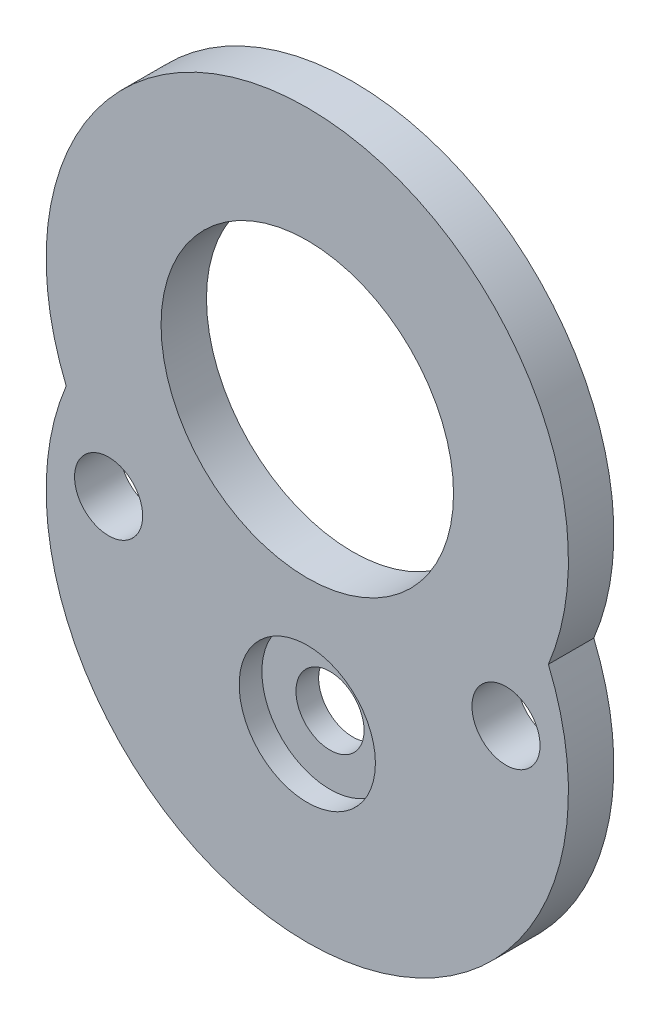
SolidWorks part; units mm, degrees
ref_plane "前视基准面" through (0, 0, 0) normal (0, 0, 1) x (1, 0, 0)
ref_plane "上视基准面" through (0, 0, 0) normal (0, 1, 0) x (1, 0, 0)
ref_plane "右视基准面" through (0, 0, 0) normal (1, 0, 0) x (0, 0, -1)
sketch "草图1" plane through (0, 0, 0) normal (0, 0, 1) x (1, 0, 0)
  line L0 (12, 12) -> (-12, 12)
  line L1 (-12, 12) -> (-12, -21.9323)
  line L2 (-12, -21.9323) -> (12, -21.9323)
  line L3 (12, -21.9323) -> (12, 12)
  line L4 (0, 0) -> (0, 17.2623) construction
  line L5 (0, 0) -> (0, -12) construction
  circle A0 centre (8.75, -7.7) radius 1.5
  circle A1 centre (0, -12) radius 3
  circle A2 centre (0, 0) radius 6.44
  circle A3 centre (-8.75, -7.7) radius 1.5
  circle A4 centre (0, -12) radius 1.5
  dimension "D1" = 12.88
  dimension "D2" = 3
  dimension "D3" = 3
  dimension "D4" = 6
  dimension "D6" = 3
  dimension "D5" = 12
  dimension "D7" = 12
extrude "凸台-拉伸1" add sketch "草图1" along normal blind 2 contours L2 L3 L0 L1 A3 A2 A1 A0 | A1 A4 region at (11.5844, -4.9661, 0) region at (-2.9151, -12, 0)
extrude "切除-拉伸1" cut sketch "草图1<3>" against normal blind 1 from surface contours A1 A4 region at (-2.9151, -12, 0) starting at face at (-7.25, -7.7, 2)
sketch "草图1<3>" plane through (0, 0, 0) normal (0, 0, 1) x (1, 0, 0) same geometry as "草图1"
sketch "草图2" plane through (0, 0, 2) normal (0, 0, 1) x (1, 0, 0)
  line L0 (0, 0) -> (0, -12) construction
  line L1 (0, 0) -> (0, -8.8386) construction
  line L2 (-8.75, -7.7) -> (8.75, -7.7) construction
  line L3 (-8.75, -7.7) -> (8.75, -7.7) construction
  line L4 (-10.617, -4.4193) -> (10.617, -4.4193) construction
  arc A0 (10.617, -4.4193) -> (-10.617, -4.4193) centre (0, 0) ccw
  arc A1 (-10.617, -4.4193) -> (10.617, -4.4193) centre (0, -8.8386) ccw
  circle A2 centre (-8.75, -7.7) radius 1.25
  circle A3 centre (8.75, -7.7) radius 1.25
  line M5 (-12, -21.9323) -> (12, -21.9323)
  line M6 (12, -21.9323) -> (12, 12)
  line M7 (12, 12) -> (-12, 12)
  line M8 (-12, 12) -> (-12, -21.9323)
  dimension "D1" = 11.5
  dimension "D2" = 11.5
  dimension "D6" = 2.5
  dimension "D3" = 17.5
  dimension "D4" = 7.7
  dimension "D5" = 21.2339
extrude "切除-拉伸3" cut sketch "草图2" against normal through all contours A1 A0 M8 M5 M6 M7 region at (-11.5844, -4.9661, 2)
